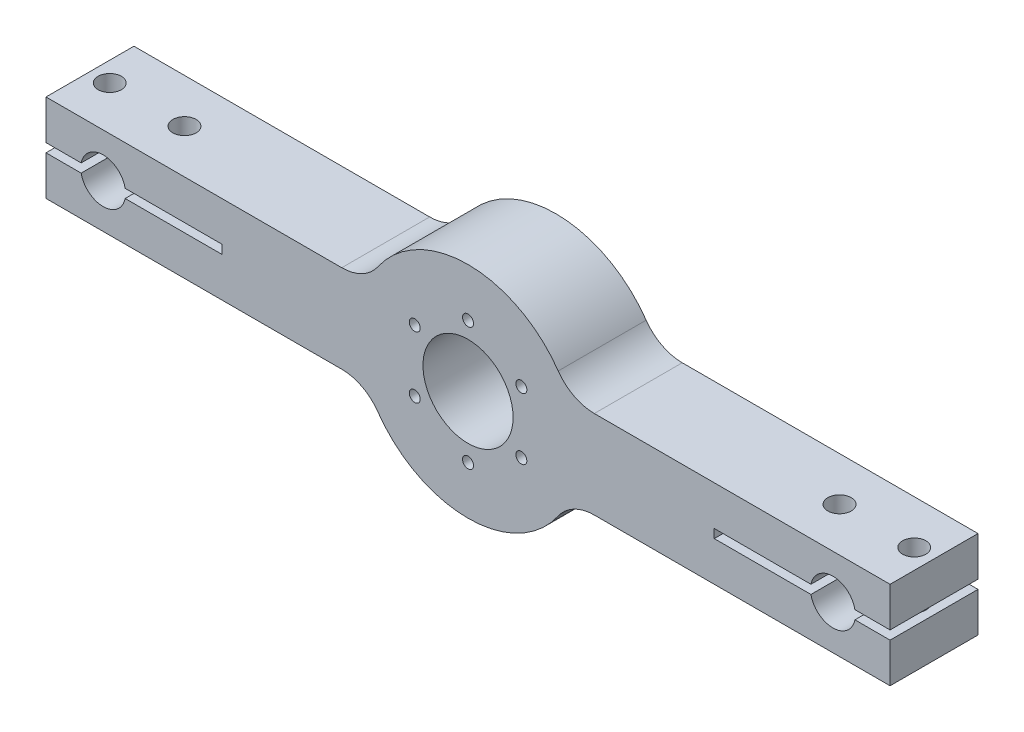
SolidWorks part; units mm, degrees
ref_plane "Alzado" through (0, 0, 0) normal (0, 0, 1) x (1, 0, 0)
ref_plane "Planta" through (0, 0, 0) normal (0, 1, 0) x (1, 0, 0)
ref_plane "Vista lateral" through (0, 0, 0) normal (1, 0, 0) x (0, 0, -1)
sketch "Croquis1" plane through (0, 0, 0) normal (0, 0, 1) x (1, 0, 0)
  line L1 (96, -10) -> (-96, -10)
  line L2 (96, -10) -> (96, 10)
  line L3 (96, 10) -> (-96, 10)
  line L4 (-96, -10) -> (-96, 10)
  line L5 (96, -10) -> (-96, 10) construction
  line L6 (96, 10) -> (-96, -10) construction
  point P0 (0, 0)
  dimension "D1" = 20
  dimension "D2" = 192
extrude "Saliente-Extruir1" add sketch "Croquis1" along normal mid plane 20
hole_wizard "Taladro de margen para M81" positions "Croquis4" profile "Croquis2" hole size "M8" standard "Ansi Metric"
sketch "Croquis4" plane through (0, 0, 10) normal (0, 0, 1) x (1, 0, 0)
  line L0 (83, 0) -> (-83, 0) construction
  point P0 (-83, 0)
  point P2 (83, 0)
  dimension "D1" = 166
sketch "Croquis2" plane through (-83, 0, 10) normal (1, 0, 0) x (0, -1, 0)
  line L0 (0, 0) -> (0, 203.0644)
  line L1 (0, 203.0644) -> (5.1, 200)
  line L2 (5.1, 200) -> (5.1, 0)
  line L5 (5.1, 0) -> (0, 0)
  line L10 (0, 203.0644) -> (-5.1, 200) construction
  line L11 (0, -6.35) -> (0, 107.95) construction
  dimension "Diámetro de taladro" = 10.2
  dimension "Profundidad de taladro" = 200
  dimension "Ángulo de perforador" = 118
sketch "Croquis5" plane through (0, 0, 10) normal (0, 0, 1) x (1, 0, 0)
  line L1 (-96, 1) -> (-56, 1)
  line L2 (-96, 1) -> (-96, -1)
  line L3 (-96, -1) -> (-56, -1)
  line L4 (-56, 1) -> (-56, -1)
  line L5 (0, 0) -> (-56, 0) construction
  line L6 (-96, 10) -> (-96, -10) construction
  dimension "D1" = 2
  dimension "D2" = 40
extrude "Cortar-Extruir1" cut sketch "Croquis5" against normal blind 20
hole_wizard "Taladro de margen para M51" positions "Croquis9" profile "Croquis8" hole size "M5" standard "Ansi Metric"
sketch "Croquis9" plane through (0, -10, 0) normal (0, -1, 0) x (-1, 0, 0)
  line L0 (96, 0) -> (91.5, 0) construction
  line L1 (96, -10) -> (96, 10) construction
  line L2 (91.5, 0) -> (74.5, 0) construction
  point P2 (91.5, 0)
  point P10 (74.5, 0)
  dimension "D1" = 4.5
  dimension "D2" = 17
sketch "Croquis8" plane through (-91.5, -10, 0) normal (1, 0, 0) x (0, 0, -1)
  line L0 (0, 0) -> (0, 201.5923)
  line L1 (0, 201.5923) -> (2.65, 200)
  line L2 (2.65, 200) -> (2.65, 0)
  line L5 (2.65, 0) -> (0, 0)
  line L10 (0, 201.5923) -> (-2.65, 200) construction
  line L11 (0, -6.35) -> (0, 107.95) construction
  dimension "Diámetro de taladro" = 5.3
  dimension "Profundidad de taladro" = 200
  dimension "Ángulo de perforador" = 118
mirror "Simetría1" about plane through (0, 0, 0) normal (1, 0, 0) of "Taladro de margen para M51", "Cortar-Extruir1"
sketch "Croquis10" plane through (0, 0, 10) normal (0, 0, 1) x (1, 0, 0)
  line L1 (55, 0) -> (-55, 0) construction
  circle A0 centre (0, 0) radius 25
  dimension "D1" = 50
extrude "Saliente-Extruir2" add sketch "Croquis10" against normal up to surface (20 mm away) up to face at (0, 0, -10)
sketch "Croquis11" plane through (0, 0, 10) normal (0, 0, 1) x (1, 0, 0)
  circle A0 centre (0, 0) radius 10.25
  dimension "D1" = 20.5
extrude "Cortar-Extruir2" cut sketch "Croquis11" against normal blind 30
fillet "Redondeo1" radius 10 4 edges at (22.9129, 10, 0) (-22.9129, 10, 0) (22.9129, -10, 0) (-22.9129, -10, 0)
hole_wizard "Taladro roscado M31" positions "Croquis13" profile "Croquis12" tap size "M3" standard "Is"
sketch "Croquis13" plane through (0, 0, 10) normal (0, 0, 1) x (1, 0, 0)
  line L0 (0, 0) -> (0, 14) construction
  point P0 (0, 14)
  dimension "D1" = 14
sketch "Croquis12" plane through (0, 14, 10) normal (1, 0, 0) x (0, -1, 0)
  line L0 (0, 0) -> (0, 20.7511)
  line L1 (0, 20.7511) -> (1.25, 20)
  line L2 (1.25, 20) -> (1.25, 0)
  line L5 (1.25, 0) -> (0, 0)
  line L10 (0, 20.7511) -> (-1.25, 20) construction
  line L11 (0, -6.35) -> (0, 107.95) construction
  dimension "Diámetro de perforador para roscar" = 2.5
  dimension "Profundidad de perforador para roscar" = 20
  dimension "Ángulo de perforador" = 118
cosmetic thread "Rosca de taladro1" parameters "D1"=20, "D2"=3
ref_axis "Eje1" through (0, 0, -10) along (0, 0, 1)
pattern_circular "MatrizC1" count 6 over 360 about axis through (0, 0, -10) along (0, 0, 1) of "Taladro roscado M31"
